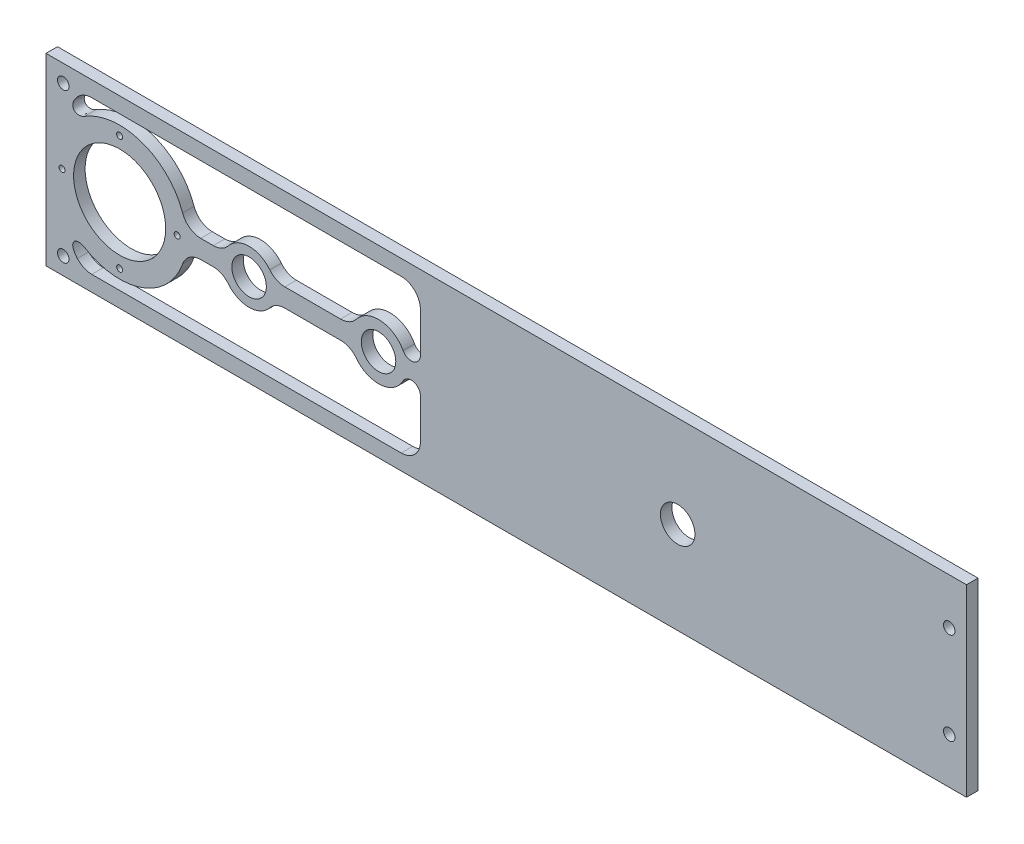
SolidWorks part; units mm, degrees
material "1060 Alloy"
ref_plane "Front Plane" through (0, 0, 0) normal (0, 0, 1) x (1, 0, 0)
ref_plane "Top Plane" through (0, 0, 0) normal (0, 1, 0) x (1, 0, 0)
ref_plane "Right Plane" through (0, 0, 0) normal (1, 0, 0) x (0, 0, -1)
sketch "Sketch1" plane through (0, 0, 0) normal (0, 0, 1) x (1, 0, 0)
  line L1 (0, 50.8) -> (508, 50.8)
  line L2 (0, 50.8) -> (0, -50.8)
  line L3 (0, -50.8) -> (508, -50.8)
  line L4 (508, 50.8) -> (508, -50.8)
  dimension "D1" = 508
  dimension "D2" = 101.6
extrude "Boss-Extrude1" add sketch "Sketch1" against normal blind 6.35
sketch "Sketch2" plane through (0, 0, 0) normal (0, 0, 1) x (1, 0, 0)
  line L0 (0, 50.8) -> (0, -50.8) construction
  circle A0 centre (40.64, 0) radius 25.4
  circle A1 centre (72.39, 0) radius 1.651
  circle A2 centre (40.64, -31.75) radius 1.651
  circle A3 centre (8.89, 0) radius 1.651
  circle A4 centre (40.64, 31.75) radius 1.651
  point P15 (40.64, 0)
  dimension "D1" = 50.8
  dimension "D2" = 3.302
  dimension "D3" = 31.75
  dimension "D4" = 40.64
  dimension "D5" = 4
extrude "Motor mount" cut sketch "Sketch2" against normal blind 6.35
sketch "Sketch3" plane through (0, 0, 0) normal (0, 0, 1) x (1, 0, 0)
  circle A0 centre (40.64, 0) radius 25.4 construction
  circle A1 centre (40.64, 0) radius 25.4 construction
  circle A2 centre (112.0775, 0) radius 9.525
  circle A3 centre (183.515, 0) radius 9.525
  circle A4 centre (348.615, 0) radius 9.525
  dimension "D1" = 19.05
  dimension "D2" = 19.05
  dimension "D5" = 19.05
  dimension "D3" = 71.4375
  dimension "D4" = 71.4375
  dimension "D6" = 165.1
extrude "Cut-Extrude2" cut sketch "Sketch3" against normal through all
sketch "Sketch4" plane through (0, 0, 0) normal (0, 0, 1) x (1, 0, 0)
  line L0 (508, 50.8) -> (0, 50.8) construction
  line L1 (0, 50.8) -> (0, -50.8) construction
  line L2 (508, -50.8) -> (508, 50.8) construction
  line L3 (0, -50.8) -> (508, -50.8) construction
  circle A0 centre (9.525, 41.275) radius 3.175
  circle A1 centre (9.525, -41.275) radius 3.175
  circle A2 centre (498.475, 25.4) radius 3.175
  circle A3 centre (498.475, -25.4) radius 3.175
  dimension "D1" = 6.35
  dimension "D2" = 6.35
  dimension "D3" = 6.35
  dimension "D4" = 6.35
  dimension "D5" = 9.525
  dimension "D6" = 9.525
  dimension "D7" = 9.525
  dimension "D8" = 25.4
  dimension "D9" = 9.525
  dimension "D10" = 25.4
extrude "Cut-Extrude3" cut sketch "Sketch4" against normal through all
sketch "Sketch7" plane through (0, 0, 0) normal (0, 0, 1) x (1, 0, 0)
  line L3 (211.7063, 0) -> (211.7063, 47.2876) construction
  line L5 (211.7063, 47.2876) -> (0, 47.2876) construction
  line L6 (0, 47.2876) -> (0, 0) construction
  line L7 (0, 0) -> (40.64, 0) construction
  line L8 (40.64, -5.08) -> (112.0775, -5.08)
  line L9 (112.0775, -5.08) -> (183.515, -5.08)
  line L10 (183.515, -5.08) -> (216.7863, -5.08)
  line L11 (216.7863, -5.08) -> (216.7863, 52.3676)
  line L12 (216.7863, 52.3676) -> (-5.08, 52.3676)
  line L13 (-5.08, 52.3676) -> (-5.08, -5.08)
  line L14 (-5.08, -5.08) -> (40.64, -5.08)
  line L15 (85.4063, 5.08) -> (92.3414, 5.08)
  line L16 (131.8136, 5.08) -> (162.5851, 5.08)
  line L18 (206.6263, 9.6628) -> (206.6263, 31.6032)
  line L19 (196.0219, 42.2076) -> (25.2631, 42.2076)
  line L20 (0, 50.8) -> (0, -50.8) construction
  line L22 (206.6263, 5.08) -> (206.6263, 42.2076) construction
  line L23 (112.0775, 5.08) -> (183.515, 5.08) construction
  line L24 (40.64, 5.08) -> (112.0775, 5.08) construction
  line L25 (206.6263, 42.2076) -> (5.08, 42.2076) construction
  line L26 (5.08, 42.2076) -> (5.08, 5.08) construction
  line L27 (112.0775, 0) -> (183.515, 0) construction
  line L28 (40.64, 0) -> (112.0775, 0) construction
  line L29 (183.515, 0) -> (211.7063, 0) construction
  line L30 (5.08, 5.08) -> (40.64, 5.08) construction
  line L31 (183.515, 5.08) -> (206.6263, 5.08) construction
  circle A0 centre (40.64, 0) radius 31.75 construction
  circle A1 centre (112.0775, 0) radius 9.525
  circle A2 centre (183.515, 0) radius 9.525
  circle A3 centre (9.525, 41.275) radius 3.1307
  arc A4 (100.6434, 9.0867) -> (92.3414, 5.08) centre (92.3414, 15.6844) cw
  arc A5 (197.0687, 7.2633) -> (206.6263, 9.6628) centre (201.5463, 9.6628) ccw
  arc A6 (17.2833, 38.5871) -> (25.2631, 42.2076) centre (25.2631, 31.6032) cw
  arc A7 (206.6263, 31.6032) -> (196.0219, 42.2076) centre (196.0219, 31.6032) ccw
  circle A8 centre (112.0775, 0) radius 4.445
  circle A9 centre (183.515, 0) radius 4.445
  circle A10 centre (40.64, 0) radius 26.67
  arc A11 (197.0687, 7.2633) -> (171.333, 9.3838) centre (183.515, 0) ccw
  arc A12 (162.5851, 5.08) -> (171.333, 9.3838) centre (162.5851, 16.1223) ccw
  arc A13 (123.5116, 9.0867) -> (100.6434, 9.0867) centre (112.0775, 0) ccw
  arc A14 (131.8136, 5.08) -> (123.5116, 9.0867) centre (131.8136, 15.6844) cw
  arc A15 (75.3984, 12.178) -> (21.2634, 31.3209) centre (40.64, 0) ccw
  arc A17 (75.3984, 12.178) -> (85.4063, 5.08) centre (85.4063, 15.6844) ccw
  spline S0 degree 3 poles (17.2833, 38.5871) (11.5305, 32.014) (16.7871, 28.5516) (21.2634, 31.3209) knots 0 0 0 0 1 1 1 1
  dimension "D1" = 5.08
  dimension "D3" = 5.08
  dimension "D4" = 11.0423
  dimension "D5" = 10.6044
  dimension "D6" = 10.6044
  dimension "D7" = 10.6044
  dimension "D2" = 5.08
extrude "Cut-Extrude4" cut sketch "Sketch7" against normal through all contours L19 A6 S0 A15 A17 L15 A4 A13 A14 L16 A12 A11 A5 L18 A7
mirror "Mirror1" about plane through (0, 0, 0) normal (0, 1, 0) of "Cut-Extrude4"
